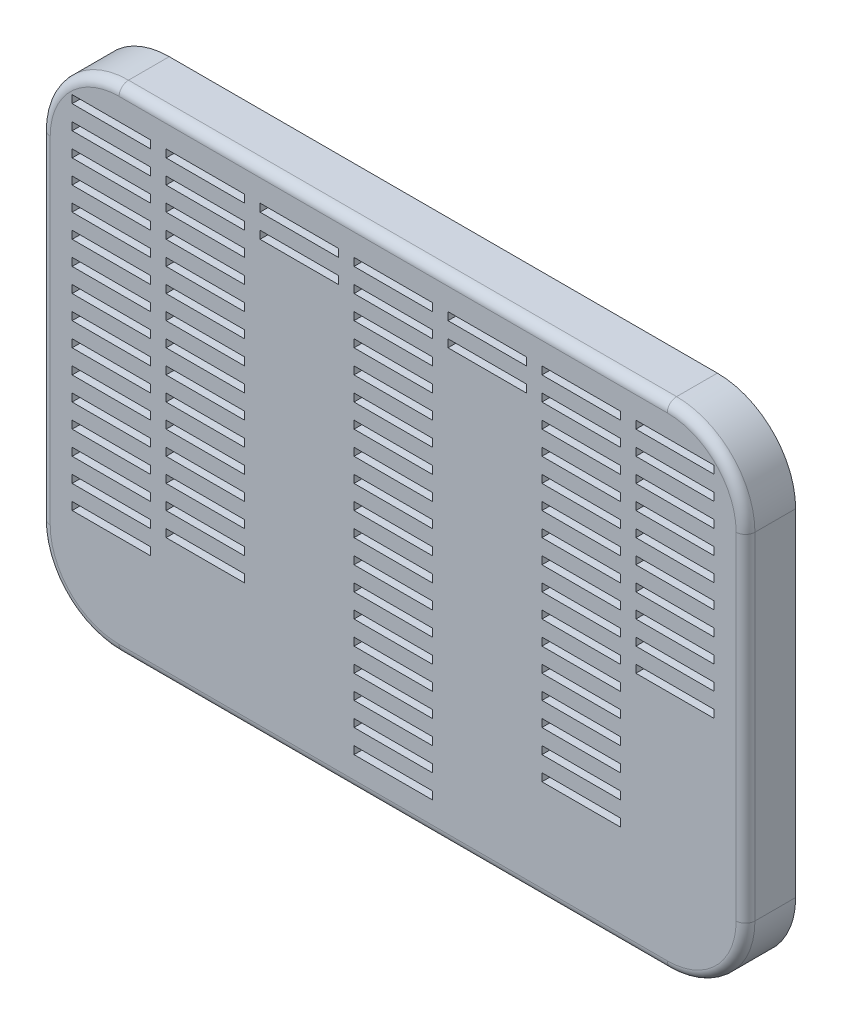
SolidWorks part; units mm, degrees
ref_plane "Front Plane" through (0, 0, 0) normal (0, 0, 1) x (1, 0, 0)
ref_plane "Top Plane" through (0, 0, 0) normal (0, 1, 0) x (1, 0, 0)
ref_plane "Right Plane" through (0, 0, 0) normal (1, 0, 0) x (0, 0, -1)
sketch "Sketch1" plane through (0, 0, 0) normal (0, 0, 1) x (1, 0, 0)
  line L0 (-62.6378, 61.2794) -> (-62.6378, 58.7794)
  line L1 (-72.6378, 71.2794) -> (152.3622, 71.2794)
  line L2 (-72.6378, 71.2794) -> (-72.6378, -86.2206)
  line L3 (-72.6378, -86.2206) -> (152.3622, -86.2206)
  line L4 (152.3622, 71.2794) -> (152.3622, -86.2206)
  line L5 (-72.6378, 71.2794) -> (-62.6378, 71.2794)
  line L6 (-72.6378, 71.2794) -> (-72.6378, 61.2794)
  line L7 (-72.6378, 61.2794) -> (-62.6378, 61.2794)
  line L8 (-62.6378, 71.2794) -> (-62.6378, 61.2794)
  line L9 (-62.6378, 58.7794) -> (-62.6378, 53.7794)
  line L10 (-62.6378, 53.7794) -> (-62.6378, 51.2794)
  line L11 (-62.6378, 51.2794) -> (-62.6378, 46.2794)
  line L12 (-62.6378, 46.2794) -> (-62.6378, 43.7794)
  line L13 (-62.6378, 43.7794) -> (-62.6378, 38.7794)
  line L14 (-62.6378, 38.7794) -> (-62.6378, 36.2794)
  line L15 (-62.6378, 36.2794) -> (-62.6378, 31.2794)
  line L16 (-62.6378, 31.2794) -> (-62.6378, 28.7794)
  line L17 (-62.6378, 28.7794) -> (-62.6378, 23.7794)
  line L18 (-62.6378, 23.7794) -> (-62.6378, 21.2794)
  line L19 (-62.6378, 21.2794) -> (-62.6378, 16.2794)
  line L20 (-62.6378, 16.2794) -> (-62.6378, 13.7794)
  line L21 (-62.6378, 13.7794) -> (-62.6378, 8.7794)
  line L22 (-62.6378, 8.7794) -> (-62.6378, 6.2794)
  line L23 (-62.6378, 6.2794) -> (-62.6378, 1.2794)
  line L24 (-62.6378, 1.2794) -> (-62.6378, -1.2206)
  line L25 (-62.6378, -1.2206) -> (-62.6378, -6.2206)
  line L26 (-62.6378, -6.2206) -> (-62.6378, -8.7206)
  line L27 (-62.6378, -8.7206) -> (-62.6378, -13.7206)
  line L28 (-62.6378, -13.7206) -> (-62.6378, -16.2206)
  line L29 (-62.6378, -16.2206) -> (-62.6378, -21.2206)
  line L30 (-62.6378, -21.2206) -> (-62.6378, -23.7206)
  line L31 (-62.6378, -23.7206) -> (-62.6378, -28.7206)
  line L32 (-62.6378, -28.7206) -> (-62.6378, -31.2206)
  line L33 (-62.6378, -31.2206) -> (-62.6378, -36.2206)
  line L34 (-62.6378, -36.2206) -> (-62.6378, -38.7206)
  line L35 (-62.6378, -38.7206) -> (-62.6378, -43.7206)
  line L36 (-62.6378, -43.7206) -> (-62.6378, -46.2206)
  line L37 (-62.6378, -46.2206) -> (-62.6378, -51.2206)
  line L38 (-62.6378, -51.2206) -> (-62.6378, -53.7206)
  line L39 (-62.6378, -53.7206) -> (-62.6378, -58.7206)
  line L40 (-62.6378, -58.7206) -> (-62.6378, -61.2206)
  line L41 (-62.6378, -61.2206) -> (-62.6378, -66.2206)
  line L42 (-62.6378, -66.2206) -> (-62.6378, -68.7206)
  line L43 (-62.6378, -68.7206) -> (-62.6378, -73.7206)
  line L44 (-62.6378, -73.7206) -> (-62.6378, -76.2206)
  line L45 (-37.6378, 61.2794) -> (-32.6378, 61.2794)
  line L46 (-62.6378, 61.2794) -> (-37.6378, 61.2794)
  line L47 (-62.6378, 61.2794) -> (-62.6378, 58.7794)
  line L48 (-62.6378, 58.7794) -> (-37.6378, 58.7794)
  line L49 (-37.6378, 61.2794) -> (-37.6378, 58.7794)
  line L50 (-7.6378, 61.2794) -> (-2.6378, 61.2794)
  line L51 (-32.6378, 61.2794) -> (-7.6378, 61.2794)
  line L52 (-32.6378, 61.2794) -> (-32.6378, 58.7794)
  line L53 (-32.6378, 58.7794) -> (-7.6378, 58.7794)
  line L54 (-7.6378, 61.2794) -> (-7.6378, 58.7794)
  line L55 (22.3622, 61.2794) -> (27.3622, 61.2794)
  line L56 (-2.6378, 61.2794) -> (22.3622, 61.2794)
  line L57 (-2.6378, 61.2794) -> (-2.6378, 58.7794)
  line L58 (-2.6378, 58.7794) -> (22.3622, 58.7794)
  line L59 (22.3622, 61.2794) -> (22.3622, 58.7794)
  line L60 (52.3622, 61.2794) -> (57.3622, 61.2794)
  line L61 (27.3622, 61.2794) -> (52.3622, 61.2794)
  line L62 (27.3622, 61.2794) -> (27.3622, 58.7794)
  line L63 (27.3622, 58.7794) -> (52.3622, 58.7794)
  line L64 (52.3622, 61.2794) -> (52.3622, 58.7794)
  line L65 (82.3622, 61.2794) -> (87.3622, 61.2794)
  line L66 (57.3622, 61.2794) -> (82.3622, 61.2794)
  line L67 (57.3622, 61.2794) -> (57.3622, 58.7794)
  line L68 (57.3622, 58.7794) -> (82.3622, 58.7794)
  line L69 (82.3622, 61.2794) -> (82.3622, 58.7794)
  line L70 (112.3622, 61.2794) -> (117.3622, 61.2794)
  line L71 (87.3622, 61.2794) -> (112.3622, 61.2794)
  line L72 (87.3622, 61.2794) -> (87.3622, 58.7794)
  line L73 (87.3622, 58.7794) -> (112.3622, 58.7794)
  line L74 (112.3622, 61.2794) -> (112.3622, 58.7794)
  line L76 (117.3622, 61.2794) -> (142.3622, 61.2794)
  line L77 (117.3622, 61.2794) -> (117.3622, 58.7794)
  line L78 (117.3622, 58.7794) -> (142.3622, 58.7794)
  line L79 (142.3622, 61.2794) -> (142.3622, 58.7794)
  line L80 (-62.6378, 53.7794) -> (-37.6378, 53.7794)
  line L81 (-62.6378, 53.7794) -> (-62.6378, 51.2794)
  line L82 (-62.6378, 51.2794) -> (-37.6378, 51.2794)
  line L83 (-37.6378, 53.7794) -> (-37.6378, 51.2794)
  line L84 (-62.6378, 46.2794) -> (-37.6378, 46.2794)
  line L85 (-62.6378, 46.2794) -> (-62.6378, 43.7794)
  line L86 (-62.6378, 43.7794) -> (-37.6378, 43.7794)
  line L87 (-37.6378, 46.2794) -> (-37.6378, 43.7794)
  line L88 (-62.6378, 38.7794) -> (-37.6378, 38.7794)
  line L89 (-62.6378, 38.7794) -> (-62.6378, 36.2794)
  line L90 (-62.6378, 36.2794) -> (-37.6378, 36.2794)
  line L91 (-37.6378, 38.7794) -> (-37.6378, 36.2794)
  line L92 (-62.6378, 31.2794) -> (-37.6378, 31.2794)
  line L93 (-62.6378, 31.2794) -> (-62.6378, 28.7794)
  line L94 (-62.6378, 28.7794) -> (-37.6378, 28.7794)
  line L95 (-37.6378, 31.2794) -> (-37.6378, 28.7794)
  line L96 (-62.6378, 23.7794) -> (-37.6378, 23.7794)
  line L97 (-62.6378, 23.7794) -> (-62.6378, 21.2794)
  line L98 (-62.6378, 21.2794) -> (-37.6378, 21.2794)
  line L99 (-37.6378, 23.7794) -> (-37.6378, 21.2794)
  line L100 (-62.6378, 16.2794) -> (-37.6378, 16.2794)
  line L101 (-62.6378, 16.2794) -> (-62.6378, 13.7794)
  line L102 (-62.6378, 13.7794) -> (-37.6378, 13.7794)
  line L103 (-37.6378, 16.2794) -> (-37.6378, 13.7794)
  line L104 (-62.6378, 8.7794) -> (-37.6378, 8.7794)
  line L105 (-62.6378, 8.7794) -> (-62.6378, 6.2794)
  line L106 (-62.6378, 6.2794) -> (-37.6378, 6.2794)
  line L107 (-37.6378, 8.7794) -> (-37.6378, 6.2794)
  line L108 (-62.6378, 1.2794) -> (-37.6378, 1.2794)
  line L109 (-62.6378, 1.2794) -> (-62.6378, -1.2206)
  line L110 (-62.6378, -1.2206) -> (-37.6378, -1.2206)
  line L111 (-37.6378, 1.2794) -> (-37.6378, -1.2206)
  line L112 (-62.6378, -6.2206) -> (-37.6378, -6.2206)
  line L113 (-62.6378, -6.2206) -> (-62.6378, -8.7206)
  line L114 (-62.6378, -8.7206) -> (-37.6378, -8.7206)
  line L115 (-37.6378, -6.2206) -> (-37.6378, -8.7206)
  line L116 (-62.6378, -13.7206) -> (-37.6378, -13.7206)
  line L117 (-62.6378, -13.7206) -> (-62.6378, -16.2206)
  line L118 (-62.6378, -16.2206) -> (-37.6378, -16.2206)
  line L119 (-37.6378, -13.7206) -> (-37.6378, -16.2206)
  line L120 (-62.6378, -21.2206) -> (-37.6378, -21.2206)
  line L121 (-62.6378, -21.2206) -> (-62.6378, -23.7206)
  line L122 (-62.6378, -23.7206) -> (-37.6378, -23.7206)
  line L123 (-37.6378, -21.2206) -> (-37.6378, -23.7206)
  line L124 (-62.6378, -28.7206) -> (-37.6378, -28.7206)
  line L125 (-62.6378, -28.7206) -> (-62.6378, -31.2206)
  line L126 (-62.6378, -31.2206) -> (-37.6378, -31.2206)
  line L127 (-37.6378, -28.7206) -> (-37.6378, -31.2206)
  line L128 (-62.6378, -36.2206) -> (-37.6378, -36.2206)
  line L129 (-62.6378, -36.2206) -> (-62.6378, -38.7206)
  line L130 (-62.6378, -38.7206) -> (-37.6378, -38.7206)
  line L131 (-37.6378, -36.2206) -> (-37.6378, -38.7206)
  line L132 (-62.6378, -43.7206) -> (-37.6378, -43.7206)
  line L133 (-62.6378, -43.7206) -> (-62.6378, -46.2206)
  line L134 (-62.6378, -46.2206) -> (-37.6378, -46.2206)
  line L135 (-37.6378, -43.7206) -> (-37.6378, -46.2206)
  line L136 (-62.6378, -51.2206) -> (-37.6378, -51.2206)
  line L137 (-62.6378, -51.2206) -> (-62.6378, -53.7206)
  line L138 (-62.6378, -53.7206) -> (-37.6378, -53.7206)
  line L139 (-37.6378, -51.2206) -> (-37.6378, -53.7206)
  line L140 (-32.6378, 53.7794) -> (-7.6378, 53.7794)
  line L141 (-32.6378, 53.7794) -> (-32.6378, 51.2794)
  line L142 (-32.6378, 51.2794) -> (-7.6378, 51.2794)
  line L143 (-7.6378, 53.7794) -> (-7.6378, 51.2794)
  line L144 (-32.6378, 46.2794) -> (-7.6378, 46.2794)
  line L145 (-32.6378, 46.2794) -> (-32.6378, 43.7794)
  line L146 (-32.6378, 43.7794) -> (-7.6378, 43.7794)
  line L147 (-7.6378, 46.2794) -> (-7.6378, 43.7794)
  line L148 (-32.6378, 38.7794) -> (-7.6378, 38.7794)
  line L149 (-32.6378, 38.7794) -> (-32.6378, 36.2794)
  line L150 (-32.6378, 36.2794) -> (-7.6378, 36.2794)
  line L151 (-7.6378, 38.7794) -> (-7.6378, 36.2794)
  line L152 (-32.6378, 31.2794) -> (-7.6378, 31.2794)
  line L153 (-32.6378, 31.2794) -> (-32.6378, 28.7794)
  line L154 (-32.6378, 28.7794) -> (-7.6378, 28.7794)
  line L155 (-7.6378, 31.2794) -> (-7.6378, 28.7794)
  line L156 (-32.6378, 23.7794) -> (-7.6378, 23.7794)
  line L157 (-32.6378, 23.7794) -> (-32.6378, 21.2794)
  line L158 (-32.6378, 21.2794) -> (-7.6378, 21.2794)
  line L159 (-7.6378, 23.7794) -> (-7.6378, 21.2794)
  line L160 (-32.6378, 16.2794) -> (-7.6378, 16.2794)
  line L161 (-32.6378, 16.2794) -> (-32.6378, 13.7794)
  line L162 (-32.6378, 13.7794) -> (-7.6378, 13.7794)
  line L163 (-7.6378, 16.2794) -> (-7.6378, 13.7794)
  line L164 (-32.6378, 8.7794) -> (-7.6378, 8.7794)
  line L165 (-32.6378, 8.7794) -> (-32.6378, 6.2794)
  line L166 (-32.6378, 6.2794) -> (-7.6378, 6.2794)
  line L167 (-7.6378, 8.7794) -> (-7.6378, 6.2794)
  line L168 (-32.6378, 1.2794) -> (-7.6378, 1.2794)
  line L169 (-32.6378, 1.2794) -> (-32.6378, -1.2206)
  line L170 (-32.6378, -1.2206) -> (-7.6378, -1.2206)
  line L171 (-7.6378, 1.2794) -> (-7.6378, -1.2206)
  line L172 (-32.6378, -6.2206) -> (-7.6378, -6.2206)
  line L173 (-32.6378, -6.2206) -> (-32.6378, -8.7206)
  line L174 (-32.6378, -8.7206) -> (-7.6378, -8.7206)
  line L175 (-7.6378, -6.2206) -> (-7.6378, -8.7206)
  line L176 (-32.6378, -13.7206) -> (-7.6378, -13.7206)
  line L177 (-32.6378, -13.7206) -> (-32.6378, -16.2206)
  line L178 (-32.6378, -16.2206) -> (-7.6378, -16.2206)
  line L179 (-7.6378, -13.7206) -> (-7.6378, -16.2206)
  line L180 (-32.6378, -21.2206) -> (-7.6378, -21.2206)
  line L181 (-32.6378, -21.2206) -> (-32.6378, -23.7206)
  line L182 (-32.6378, -23.7206) -> (-7.6378, -23.7206)
  line L183 (-7.6378, -21.2206) -> (-7.6378, -23.7206)
  line L184 (-32.6378, -28.7206) -> (-7.6378, -28.7206)
  line L185 (-32.6378, -28.7206) -> (-32.6378, -31.2206)
  line L186 (-32.6378, -31.2206) -> (-7.6378, -31.2206)
  line L187 (-7.6378, -28.7206) -> (-7.6378, -31.2206)
  line L188 (-32.6378, -36.2206) -> (-7.6378, -36.2206)
  line L189 (-32.6378, -36.2206) -> (-32.6378, -38.7206)
  line L190 (-32.6378, -38.7206) -> (-7.6378, -38.7206)
  line L191 (-7.6378, -36.2206) -> (-7.6378, -38.7206)
  line L192 (-32.6378, -43.7206) -> (-7.6378, -43.7206)
  line L193 (-32.6378, -43.7206) -> (-32.6378, -46.2206)
  line L194 (-32.6378, -46.2206) -> (-7.6378, -46.2206)
  line L195 (-7.6378, -43.7206) -> (-7.6378, -46.2206)
  line L196 (-2.6378, 53.7794) -> (22.3622, 53.7794)
  line L197 (-2.6378, 53.7794) -> (-2.6378, 51.2794)
  line L198 (-2.6378, 51.2794) -> (22.3622, 51.2794)
  line L199 (22.3622, 53.7794) -> (22.3622, 51.2794)
  line L200 (27.3622, 53.7794) -> (52.3622, 53.7794)
  line L201 (27.3622, 53.7794) -> (27.3622, 51.2794)
  line L202 (27.3622, 51.2794) -> (52.3622, 51.2794)
  line L203 (52.3622, 53.7794) -> (52.3622, 51.2794)
  line L204 (27.3622, 46.2794) -> (52.3622, 46.2794)
  line L205 (27.3622, 46.2794) -> (27.3622, 43.7794)
  line L206 (27.3622, 43.7794) -> (52.3622, 43.7794)
  line L207 (52.3622, 46.2794) -> (52.3622, 43.7794)
  line L208 (27.3622, 38.7794) -> (52.3622, 38.7794)
  line L209 (27.3622, 38.7794) -> (27.3622, 36.2794)
  line L210 (27.3622, 36.2794) -> (52.3622, 36.2794)
  line L211 (52.3622, 38.7794) -> (52.3622, 36.2794)
  line L212 (27.3622, 31.2794) -> (52.3622, 31.2794)
  line L213 (27.3622, 31.2794) -> (27.3622, 28.7794)
  line L214 (27.3622, 28.7794) -> (52.3622, 28.7794)
  line L215 (52.3622, 31.2794) -> (52.3622, 28.7794)
  line L216 (27.3622, 23.7794) -> (52.3622, 23.7794)
  line L217 (27.3622, 23.7794) -> (27.3622, 21.2794)
  line L218 (27.3622, 21.2794) -> (52.3622, 21.2794)
  line L219 (52.3622, 23.7794) -> (52.3622, 21.2794)
  line L220 (27.3622, 16.2794) -> (52.3622, 16.2794)
  line L221 (27.3622, 16.2794) -> (27.3622, 13.7794)
  line L222 (27.3622, 13.7794) -> (52.3622, 13.7794)
  line L223 (52.3622, 16.2794) -> (52.3622, 13.7794)
  line L224 (27.3622, 8.7794) -> (52.3622, 8.7794)
  line L225 (27.3622, 8.7794) -> (27.3622, 6.2794)
  line L226 (27.3622, 6.2794) -> (52.3622, 6.2794)
  line L227 (52.3622, 8.7794) -> (52.3622, 6.2794)
  line L228 (27.3622, 1.2794) -> (52.3622, 1.2794)
  line L229 (27.3622, 1.2794) -> (27.3622, -1.2206)
  line L230 (27.3622, -1.2206) -> (52.3622, -1.2206)
  line L231 (52.3622, 1.2794) -> (52.3622, -1.2206)
  line L232 (27.3622, -6.2206) -> (52.3622, -6.2206)
  line L233 (27.3622, -6.2206) -> (27.3622, -8.7206)
  line L234 (27.3622, -8.7206) -> (52.3622, -8.7206)
  line L235 (52.3622, -6.2206) -> (52.3622, -8.7206)
  line L236 (27.3622, -13.7206) -> (52.3622, -13.7206)
  line L237 (27.3622, -13.7206) -> (27.3622, -16.2206)
  line L238 (27.3622, -16.2206) -> (52.3622, -16.2206)
  line L239 (52.3622, -13.7206) -> (52.3622, -16.2206)
  line L240 (27.3622, -21.2206) -> (52.3622, -21.2206)
  line L241 (27.3622, -21.2206) -> (27.3622, -23.7206)
  line L242 (27.3622, -23.7206) -> (52.3622, -23.7206)
  line L243 (52.3622, -21.2206) -> (52.3622, -23.7206)
  line L244 (27.3622, -28.7206) -> (52.3622, -28.7206)
  line L245 (27.3622, -28.7206) -> (27.3622, -31.2206)
  line L246 (27.3622, -31.2206) -> (52.3622, -31.2206)
  line L247 (52.3622, -28.7206) -> (52.3622, -31.2206)
  line L248 (27.3622, -36.2206) -> (52.3622, -36.2206)
  line L249 (27.3622, -36.2206) -> (27.3622, -38.7206)
  line L250 (27.3622, -38.7206) -> (52.3622, -38.7206)
  line L251 (52.3622, -36.2206) -> (52.3622, -38.7206)
  line L252 (27.3622, -43.7206) -> (52.3622, -43.7206)
  line L253 (27.3622, -43.7206) -> (27.3622, -46.2206)
  line L254 (27.3622, -46.2206) -> (52.3622, -46.2206)
  line L255 (52.3622, -43.7206) -> (52.3622, -46.2206)
  line L256 (27.3622, -51.2206) -> (52.3622, -51.2206)
  line L257 (27.3622, -51.2206) -> (27.3622, -53.7206)
  line L258 (27.3622, -53.7206) -> (52.3622, -53.7206)
  line L259 (52.3622, -51.2206) -> (52.3622, -53.7206)
  line L260 (27.3622, -58.7206) -> (52.3622, -58.7206)
  line L261 (27.3622, -58.7206) -> (27.3622, -61.2206)
  line L262 (27.3622, -61.2206) -> (52.3622, -61.2206)
  line L263 (52.3622, -58.7206) -> (52.3622, -61.2206)
  line L264 (27.3622, -66.2206) -> (52.3622, -66.2206)
  line L265 (27.3622, -66.2206) -> (27.3622, -68.7206)
  line L266 (27.3622, -68.7206) -> (52.3622, -68.7206)
  line L267 (52.3622, -66.2206) -> (52.3622, -68.7206)
  line L268 (27.3622, -73.7206) -> (52.3622, -73.7206)
  line L269 (27.3622, -73.7206) -> (27.3622, -76.2206)
  line L270 (27.3622, -76.2206) -> (52.3622, -76.2206)
  line L271 (52.3622, -73.7206) -> (52.3622, -76.2206)
  line L272 (57.3622, 53.7794) -> (82.3622, 53.7794)
  line L273 (57.3622, 53.7794) -> (57.3622, 51.2794)
  line L274 (57.3622, 51.2794) -> (82.3622, 51.2794)
  line L275 (82.3622, 53.7794) -> (82.3622, 51.2794)
  line L276 (87.3622, 53.7794) -> (112.3622, 53.7794)
  line L277 (87.3622, 53.7794) -> (87.3622, 51.2794)
  line L278 (87.3622, 51.2794) -> (112.3622, 51.2794)
  line L279 (112.3622, 53.7794) -> (112.3622, 51.2794)
  line L280 (87.3622, 46.2794) -> (112.3622, 46.2794)
  line L281 (87.3622, 46.2794) -> (87.3622, 43.7794)
  line L282 (87.3622, 43.7794) -> (112.3622, 43.7794)
  line L283 (112.3622, 46.2794) -> (112.3622, 43.7794)
  line L284 (87.3622, 38.7794) -> (112.3622, 38.7794)
  line L285 (87.3622, 38.7794) -> (87.3622, 36.2794)
  line L286 (87.3622, 36.2794) -> (112.3622, 36.2794)
  line L287 (112.3622, 38.7794) -> (112.3622, 36.2794)
  line L288 (87.3622, 31.2794) -> (112.3622, 31.2794)
  line L289 (87.3622, 31.2794) -> (87.3622, 28.7794)
  line L290 (87.3622, 28.7794) -> (112.3622, 28.7794)
  line L291 (112.3622, 31.2794) -> (112.3622, 28.7794)
  line L292 (87.3622, 23.7794) -> (112.3622, 23.7794)
  line L293 (87.3622, 23.7794) -> (87.3622, 21.2794)
  line L294 (87.3622, 21.2794) -> (112.3622, 21.2794)
  line L295 (112.3622, 23.7794) -> (112.3622, 21.2794)
  line L296 (87.3622, 16.2794) -> (112.3622, 16.2794)
  line L297 (87.3622, 16.2794) -> (87.3622, 13.7794)
  line L298 (87.3622, 13.7794) -> (112.3622, 13.7794)
  line L299 (112.3622, 16.2794) -> (112.3622, 13.7794)
  line L300 (87.3622, 8.7794) -> (112.3622, 8.7794)
  line L301 (87.3622, 8.7794) -> (87.3622, 6.2794)
  line L302 (87.3622, 6.2794) -> (112.3622, 6.2794)
  line L303 (112.3622, 8.7794) -> (112.3622, 6.2794)
  line L304 (87.3622, 1.2794) -> (112.3622, 1.2794)
  line L305 (87.3622, 1.2794) -> (87.3622, -1.2206)
  line L306 (87.3622, -1.2206) -> (112.3622, -1.2206)
  line L307 (112.3622, 1.2794) -> (112.3622, -1.2206)
  line L308 (87.3622, -6.2206) -> (112.3622, -6.2206)
  line L309 (87.3622, -6.2206) -> (87.3622, -8.7206)
  line L310 (87.3622, -8.7206) -> (112.3622, -8.7206)
  line L311 (112.3622, -6.2206) -> (112.3622, -8.7206)
  line L312 (87.3622, -13.7206) -> (112.3622, -13.7206)
  line L313 (87.3622, -13.7206) -> (87.3622, -16.2206)
  line L314 (87.3622, -16.2206) -> (112.3622, -16.2206)
  line L315 (112.3622, -13.7206) -> (112.3622, -16.2206)
  line L316 (87.3622, -21.2206) -> (112.3622, -21.2206)
  line L317 (87.3622, -21.2206) -> (87.3622, -23.7206)
  line L318 (87.3622, -23.7206) -> (112.3622, -23.7206)
  line L319 (112.3622, -21.2206) -> (112.3622, -23.7206)
  line L320 (87.3622, -28.7206) -> (112.3622, -28.7206)
  line L321 (87.3622, -28.7206) -> (87.3622, -31.2206)
  line L322 (87.3622, -31.2206) -> (112.3622, -31.2206)
  line L323 (112.3622, -28.7206) -> (112.3622, -31.2206)
  line L324 (87.3622, -36.2206) -> (112.3622, -36.2206)
  line L325 (87.3622, -36.2206) -> (87.3622, -38.7206)
  line L326 (87.3622, -38.7206) -> (112.3622, -38.7206)
  line L327 (112.3622, -36.2206) -> (112.3622, -38.7206)
  line L328 (87.3622, -43.7206) -> (112.3622, -43.7206)
  line L329 (87.3622, -43.7206) -> (87.3622, -46.2206)
  line L330 (87.3622, -46.2206) -> (112.3622, -46.2206)
  line L331 (112.3622, -43.7206) -> (112.3622, -46.2206)
  line L332 (87.3622, -51.2206) -> (112.3622, -51.2206)
  line L333 (87.3622, -51.2206) -> (87.3622, -53.7206)
  line L334 (87.3622, -53.7206) -> (112.3622, -53.7206)
  line L335 (112.3622, -51.2206) -> (112.3622, -53.7206)
  line L336 (117.3622, 53.7794) -> (142.3622, 53.7794)
  line L337 (117.3622, 53.7794) -> (117.3622, 51.2794)
  line L338 (117.3622, 51.2794) -> (142.3622, 51.2794)
  line L339 (142.3622, 53.7794) -> (142.3622, 51.2794)
  line L340 (117.3622, 46.2794) -> (142.3622, 46.2794)
  line L341 (117.3622, 46.2794) -> (117.3622, 43.7794)
  line L342 (117.3622, 43.7794) -> (142.3622, 43.7794)
  line L343 (142.3622, 46.2794) -> (142.3622, 43.7794)
  line L344 (117.3622, 38.7794) -> (142.3622, 38.7794)
  line L345 (117.3622, 38.7794) -> (117.3622, 36.2794)
  line L346 (117.3622, 36.2794) -> (142.3622, 36.2794)
  line L347 (142.3622, 38.7794) -> (142.3622, 36.2794)
  line L348 (117.3622, 31.2794) -> (142.3622, 31.2794)
  line L349 (117.3622, 31.2794) -> (117.3622, 28.7794)
  line L350 (117.3622, 28.7794) -> (142.3622, 28.7794)
  line L351 (142.3622, 31.2794) -> (142.3622, 28.7794)
  line L352 (117.3622, 23.7794) -> (142.3622, 23.7794)
  line L353 (117.3622, 23.7794) -> (117.3622, 21.2794)
  line L354 (117.3622, 21.2794) -> (142.3622, 21.2794)
  line L355 (142.3622, 23.7794) -> (142.3622, 21.2794)
  line L356 (117.3622, 16.2794) -> (142.3622, 16.2794)
  line L357 (117.3622, 16.2794) -> (117.3622, 13.7794)
  line L358 (117.3622, 13.7794) -> (142.3622, 13.7794)
  line L359 (142.3622, 16.2794) -> (142.3622, 13.7794)
  line L360 (117.3622, 8.7794) -> (142.3622, 8.7794)
  line L361 (117.3622, 8.7794) -> (117.3622, 6.2794)
  line L362 (117.3622, 6.2794) -> (142.3622, 6.2794)
  line L363 (142.3622, 8.7794) -> (142.3622, 6.2794)
  line L364 (117.3622, 1.2794) -> (142.3622, 1.2794)
  line L365 (117.3622, 1.2794) -> (117.3622, -1.2206)
  line L366 (117.3622, -1.2206) -> (142.3622, -1.2206)
  line L367 (142.3622, 1.2794) -> (142.3622, -1.2206)
  line L368 (117.3622, -6.2206) -> (142.3622, -6.2206)
  line L369 (117.3622, -6.2206) -> (117.3622, -8.7206)
  line L370 (117.3622, -8.7206) -> (142.3622, -8.7206)
  line L371 (142.3622, -6.2206) -> (142.3622, -8.7206)
  dimension "D1" = 225
  dimension "D2" = 157.5
  dimension "D3" = 10
  dimension "D4" = 10
  dimension "D5" = 2.5
  dimension "D6" = 5
  dimension "D7" = 25
  dimension "D8" = 5
extrude "Boss-Extrude1" add sketch "Sketch1" along normal blind 2 contours L136 L139 L138 L38 L36 L34 L32 L30 L28 L26 L24 L22 L20 L18 L16 L14 L12 L10 L0 L7 L2 L3 L4 L1 | L8 L1 L2 L7 | L49 L46 L0 L48 | L83 L80 L10 L82 | L87 L84 L12 L86 | L91 L88 L14 L90 | L95 L92 L16 L94 | L99 L96 L18 L98 | L103 L100 L20 L102 | L107 L104 L22 L106 | L111 L108 L24 L110 | L115 L112 L26 L114 | L119 L116 L28 L118 | L123 L120 L30 L122 | L127 L124 L32 L126 | L131 L128 L34 L130 | L135 L132 L36 L134 | L139 L136 L38 L138 | L195 L192 L193 L194 | L191 L188 L189 L190 | L187 L184 L185 L186 | L183 L180 L181 L182 | L179 L176 L177 L178 | L175 L172 L173 L174 | L171 L168 L169 L170 | L167 L164 L165 L166 | L163 L160 L161 L162 | L159 L156 L157 L158 | L155 L152 L153 L154 | L151 L148 L149 L150 | L147 L144 L145 L146 | L143 L140 L141 L142 | L54 L51 L52 L53 | L59 L56 L57 L58 | L199 L196 L197 L198 | L64 L61 L62 L63 | L203 L200 L201 L202 | L207 L204 L205 L206 | L211 L208 L209 L210 | L215 L212 L213 L214 | L219 L216 L217 L218 | L223 L220 L221 L222 | L227 L224 L225 L226 | L231 L228 L229 L230 | L235 L232 L233 L234 | L239 L236 L237 L238 | L243 L240 L241 L242 | L247 L244 L245 L246 | L251 L248 L249 L250 | L255 L252 L253 L254 | L259 L256 L257 L258 | L263 L260 L261 L262 | L267 L264 L265 L266 | L271 L268 L269 L270 | L69 L66 L67 L68 | L275 L272 L273 L274 | L74 L71 L72 L73 | L279 L276 L277 L278 | L283 L280 L281 L282 | L287 L284 L285 L286 | L291 L288 L289 L290 | L295 L292 L293 L294 | L299 L296 L297 L298 | L303 L300 L301 L302 | L307 L304 L305 L306 | L311 L308 L309 L310 | L315 L312 L313 L314 | L319 L316 L317 L318 | L323 L320 L321 L322 | L327 L324 L325 L326 | L331 L328 L329 L330 | L335 L332 L333 L334 | L79 L76 L77 L78 | L339 L336 L337 L338 | L343 L340 L341 L342 | L347 L344 L345 L346 | L351 L348 L349 L350 | L355 L352 L353 L354 | L359 L356 L357 L358 | L363 L360 L361 L362 | L367 L364 L365 L366 | L371 L368 L369 L370 region at (-50.1378, 60.0294, 0) region at (41.2054, -10.1395, 0) region at (-67.6378, 66.2794, 0) region at (129.8622, 60.0294, 0) region at (99.8622, 60.0294, 0) region at (69.8622, 60.0294, 0) region at (39.8622, 60.0294, 0) region at (9.8622, 60.0294, 0) region at (-20.1378, 60.0294, 0) region at (-50.1378, -52.4706, 0) region at (-50.1378, -44.9706, 0) region at (-50.1378, -37.4706, 0) region at (-50.1378, -29.9706, 0) region at (-50.1378, -22.4706, 0) region at (-50.1378, -14.9706, 0) region at (-50.1378, -7.4706, 0) region at (-50.1378, 0.0294, 0) region at (-50.1378, 7.5294, 0) region at (-50.1378, 15.0294, 0) region at (-50.1378, 22.5294, 0) region at (-50.1378, 30.0294, 0) region at (-50.1378, 37.5294, 0) region at (-50.1378, 45.0294, 0) region at (-50.1378, 52.5294, 0) region at (-20.1378, 52.5294, 0) region at (-20.1378, 45.0294, 0) region at (-20.1378, 37.5294, 0) region at (-20.1378, 30.0294, 0) region at (-20.1378, 22.5294, 0) region at (-20.1378, 15.0294, 0) region at (-20.1378, 7.5294, 0) region at (-20.1378, 0.0294, 0) region at (-20.1378, -7.4706, 0) region at (-20.1378, -14.9706, 0) region at (-20.1378, -22.4706, 0) region at (-20.1378, -29.9706, 0) region at (-20.1378, -37.4706, 0) region at (-20.1378, -44.9706, 0) region at (9.8622, 52.5294, 0) region at (39.8622, 52.5294, 0) region at (39.8622, 45.0294, 0) region at (39.8622, 37.5294, 0) region at (39.8622, 30.0294, 0) region at (39.8622, 22.5294, 0) region at (39.8622, 15.0294, 0) region at (39.8622, 7.5294, 0) region at (39.8622, 0.0294, 0) region at (39.8622, -7.4706, 0) region at (39.8622, -14.9706, 0) region at (39.8622, -22.4706, 0) region at (39.8622, -29.9706, 0) region at (39.8622, -37.4706, 0) region at (39.8622, -44.9706, 0) region at (39.8622, -52.4706, 0) region at (39.8622, -59.9706, 0) region at (39.8622, -67.4706, 0) region at (39.8622, -74.9706, 0) region at (69.8622, 52.5294, 0) region at (99.8622, 52.5294, 0) region at (99.8622, 45.0294, 0)
extrude "Boss-Extrude2" add sketch "Sketch1<3>" along normal blind 16 contours L136 L139 L138 L38 L36 L34 L32 L30 L28 L26 L24 L22 L20 L18 L16 L14 L12 L10 L0 L7 L2 L3 L4 L1 | L8 L1 L2 L7 region at (41.2054, -10.1395, 0) region at (-67.6378, 66.2794, 0)
sketch "Sketch1<3>" plane through (0, 0, 0) normal (0, 0, 1) x (1, 0, 0) same geometry as "Sketch1"
fillet "Fillet1" radius 25 4 edges at (-72.6378, 71.2794, 8) (-72.6378, -86.2206, 8) (152.3622, -86.2206, 8) (152.3622, 71.2794, 8)
fillet "Fillet2" radius 3 8 edges at (-65.3155, 63.9571, 16) (-72.6378, -7.4706, 16) (-65.3155, -78.8982, 16) (39.8622, -86.2206, 16) (145.0399, -78.8982, 16) (152.3622, -7.4706, 16) (145.0399, 63.9571, 16) (39.8622, 71.2794, 16)
